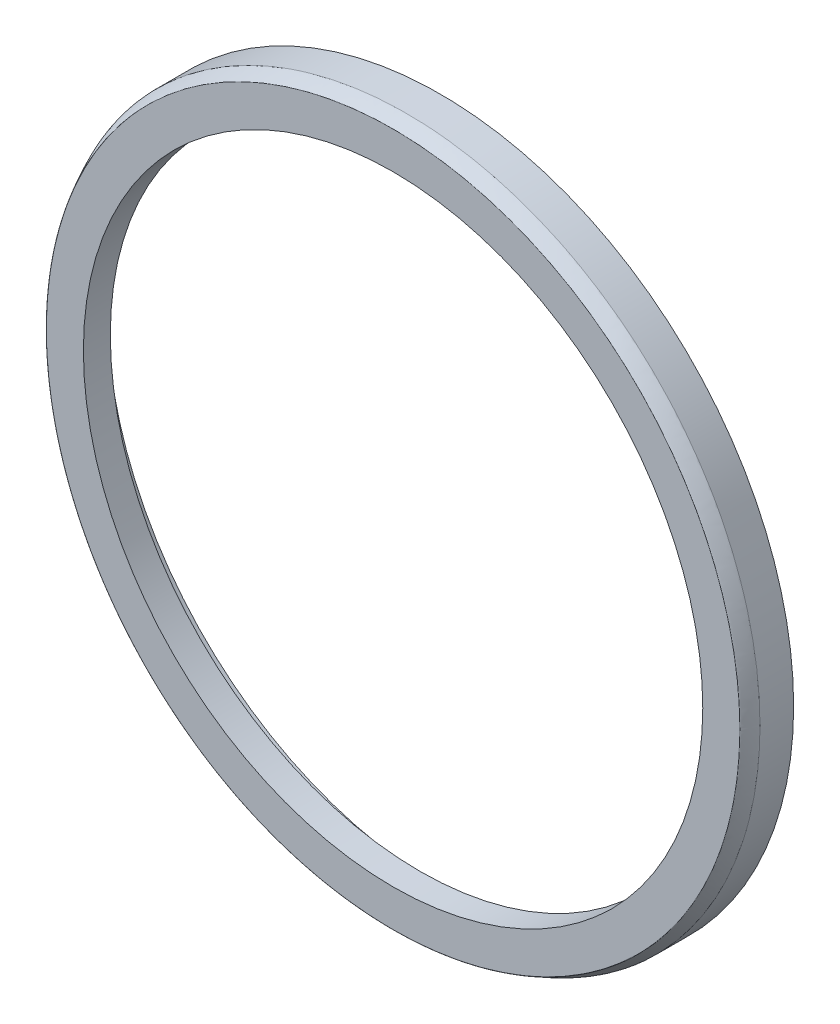
SolidWorks part; units mm, degrees
ref_plane "Front Plane" through (0, 0, 0) normal (0, 0, 1) x (1, 0, 0)
ref_plane "Top Plane" through (0, 0, 0) normal (0, 1, 0) x (1, 0, 0)
ref_plane "Right Plane" through (0, 0, 0) normal (1, 0, 0) x (0, 0, -1)
sketch "Sketch3" plane through (0, 0, 0) normal (0, 0, 1) x (1, 0, 0)
  circle A0 centre (0, 0) radius 52.5
  dimension "D1" = 105
extrude "Boss-Extrude2" add sketch "Sketch3" along normal blind 4
sketch "Sketch4" plane through (0, 0, 0) normal (0, 0, -1) x (-1, 0, 0)
  circle A0 centre (0, 0) radius 52.5
  circle A1 centre (0, 0) radius 49.5
  dimension "D2" = 105
  dimension "D1" = 3
extrude "Boss-Extrude3" add sketch "Sketch4" along normal blind 3
sketch "Sketch5" plane through (0, 0, 0) normal (0, 0, -1) x (-1, 0, 0)
  circle A0 centre (0, 0) radius 46
  dimension "D1" = 92
  dimension "D2" = 0
extrude "Cut-Extrude1" cut sketch "Sketch5" against normal blind 10
fillet "Fillet1" radius 2 1 edges at (52.5, 0, 4) second distance 1 conic rho 0.05 first distance on face at (52.5, 0, 4)
